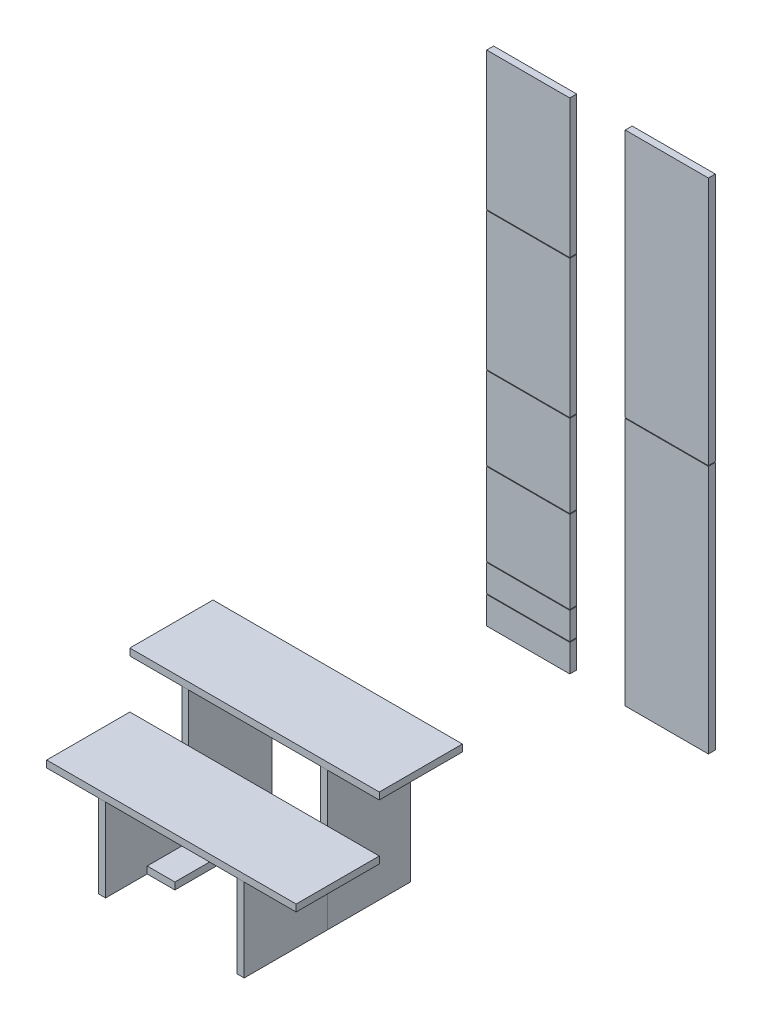
SolidWorks part; units mm, degrees
other "DetailItem1"
ref_plane "Front Plane" through (0, 0, 0) normal (0, 0, 1) x (1, 0, 0)
ref_plane "Top Plane" through (0, 0, 0) normal (0, 1, 0) x (1, 0, 0)
ref_plane "Right Plane" through (0, 0, 0) normal (1, 0, 0) x (0, 0, -1)
sketch "Sketch1" plane through (0, 0, 0) normal (0, 1, 0) x (1, 0, 0)
  line L0 (-254, 0) -> (254, 0) construction
  line L2 (-266.7, 152.4) -> (-241.3, 152.4)
  line L3 (-266.7, 152.4) -> (-266.7, -152.4)
  line L4 (-266.7, -152.4) -> (-241.3, -152.4)
  line L5 (-241.3, 152.4) -> (-241.3, -152.4)
  line L6 (-266.7, 152.4) -> (-241.3, -152.4) construction
  line L7 (-266.7, -152.4) -> (-241.3, 152.4) construction
  line L8 (241.3, 152.4) -> (266.7, 152.4)
  line L9 (241.3, 152.4) -> (241.3, -152.4)
  line L10 (241.3, -152.4) -> (266.7, -152.4)
  line L11 (266.7, 152.4) -> (266.7, -152.4)
  line L12 (241.3, 152.4) -> (266.7, -152.4) construction
  line L13 (241.3, -152.4) -> (266.7, 152.4) construction
  dimension "D1" = 25.4
  dimension "D2" = 304.8
  dimension "D3" = 508
extrude "Boss-Extrude1" add sketch "Sketch1" along normal blind 508
sketch "Sketch2" plane through (0, 508, 0) normal (0, 1, 0) x (1, 0, 0)
  line L0 (-241.3, 152.4) -> (-266.7, 152.4) construction
  line L1 (-457.2, -152.4) -> (457.2, -152.4)
  line L2 (-457.2, -152.4) -> (-457.2, 152.4)
  line L3 (-457.2, 152.4) -> (457.2, 152.4)
  line L4 (457.2, -152.4) -> (457.2, 152.4)
  line L5 (-457.2, -152.4) -> (457.2, 152.4) construction
  line L6 (-457.2, 152.4) -> (457.2, -152.4) construction
  point P0 (0, 0)
  dimension "D1" = 914.4
extrude "Boss-Extrude2" add sketch "Sketch2" along normal blind 25.4 separate body
sketch "Sketch3" plane through (0, 0, 0) normal (0, 1, 0) x (1, 0, 0)
  line L0 (-254, -304.8) -> (254, -304.8) construction
  line L1 (-457.2, -152.4) -> (457.2, -152.4) construction
  line L2 (-266.7, -152.4) -> (-241.3, -152.4)
  line L3 (-266.7, -152.4) -> (-266.7, -457.2)
  line L4 (-266.7, -457.2) -> (-241.3, -457.2)
  line L5 (-241.3, -152.4) -> (-241.3, -457.2)
  line L6 (-266.7, -152.4) -> (-241.3, -457.2) construction
  line L7 (-266.7, -457.2) -> (-241.3, -152.4) construction
  line L8 (241.3, -152.4) -> (266.7, -152.4)
  line L9 (241.3, -152.4) -> (241.3, -457.2)
  line L10 (241.3, -457.2) -> (266.7, -457.2)
  line L11 (266.7, -152.4) -> (266.7, -457.2)
  line L12 (241.3, -152.4) -> (266.7, -457.2) construction
  line L13 (241.3, -457.2) -> (266.7, -152.4) construction
  point P2 (0, -304.8)
  dimension "D1" = 25.4
  dimension "D2" = 304.8
  dimension "D3" = 508
extrude "Boss-Extrude3" add sketch "Sketch3" along normal blind 304.8 separate body
sketch "Sketch4" plane through (0, 304.8, 0) normal (0, 1, 0) x (1, 0, 0)
  line L0 (-457.2, -152.4) -> (457.2, -152.4) construction
  line L1 (-457.2, -457.2) -> (457.2, -457.2)
  line L2 (-457.2, -457.2) -> (-457.2, -152.4)
  line L3 (-457.2, -152.4) -> (457.2, -152.4)
  line L4 (457.2, -457.2) -> (457.2, -152.4)
  line L5 (-457.2, -457.2) -> (457.2, -152.4) construction
  line L6 (-457.2, -152.4) -> (457.2, -457.2) construction
  line L7 (-266.7, -457.2) -> (-241.3, -457.2) construction
  point P0 (0, -304.8)
  dimension "D1" = 914.4
extrude "Boss-Extrude4" add sketch "Sketch4" along normal blind 25.4 separate body
sketch "Sketch5" plane through (0, 0, 0) normal (0, 1, 0) x (1, 0, 0)
  line L0 (0, 0) -> (0, 1117.6) construction
  line L1 (-254, 1117.6) -> (254, 1117.6) construction
  line L3 (-406.4, 1130.3) -> (-101.6, 1130.3)
  line L4 (-406.4, 1130.3) -> (-406.4, 1104.9)
  line L5 (-406.4, 1104.9) -> (-101.6, 1104.9)
  line L6 (-101.6, 1130.3) -> (-101.6, 1104.9)
  line L7 (-406.4, 1130.3) -> (-101.6, 1104.9) construction
  line L8 (-406.4, 1104.9) -> (-101.6, 1130.3) construction
  line L9 (101.6, 1130.3) -> (406.4, 1130.3)
  line L10 (101.6, 1130.3) -> (101.6, 1104.9)
  line L11 (101.6, 1104.9) -> (406.4, 1104.9)
  line L12 (406.4, 1130.3) -> (406.4, 1104.9)
  line L13 (101.6, 1130.3) -> (406.4, 1104.9) construction
  line L14 (101.6, 1104.9) -> (406.4, 1130.3) construction
  point P5 (0, 1117.6)
  dimension "D1" = 25.4
  dimension "D2" = 304.8
  dimension "D3" = 25.4
  dimension "D4" = 304.8
  dimension "D5" = 1117.6
  dimension "D6" = 508
extrude "Boss-Extrude5" add sketch "Sketch5" along normal blind 1828.8 separate body
sketch "Sketch6" plane through (0, 0, -1130.3) normal (0, 0, -1) x (-1, 0, 0)
  line L0 (-406.4, 914.4) -> (-101.6, 914.4)
  line L1 (-406.4, 1828.8) -> (-406.4, 0) construction
  line L2 (-101.6, 1828.8) -> (-101.6, 0) construction
  line L3 (101.6, 1320.8) -> (406.4, 1320.8)
  line L4 (101.6, 1828.8) -> (101.6, 0) construction
  line L5 (406.4, 1828.8) -> (406.4, 0) construction
  line L6 (101.6, 812.8) -> (406.4, 812.8)
  line L7 (101.6, 508) -> (406.4, 508)
  line L8 (101.6, 203.2) -> (406.4, 203.2)
  line L9 (101.6, 101.6) -> (406.4, 101.6)
  line L10 (101.6, 1828.8) -> (406.4, 1828.8) construction
  line L11 (101.6, 0) -> (406.4, 0) construction
  dimension "D1" = 508
  dimension "D2" = 508
  dimension "D3" = 304.8
  dimension "D4" = 304.8
  dimension "D5" = 101.6
sketch "Sketch7" plane through (0, 0, 0) normal (0, -1, 0) x (1, 0, 0)
  line L0 (-241.3, 152.4) -> (241.3, 152.4) construction
  line L1 (241.3, -152.4) -> (241.3, 152.4) construction
  line L2 (-241.3, 304.8) -> (241.3, 304.8)
  line L3 (-241.3, 304.8) -> (-241.3, 0)
  line L4 (-241.3, 0) -> (241.3, 0)
  line L5 (241.3, 304.8) -> (241.3, 0)
  line L6 (-241.3, 304.8) -> (241.3, 0) construction
  line L7 (-241.3, 0) -> (241.3, 304.8) construction
  line L8 (-139.7, 304.8) -> (-139.7, 0)
  line L9 (139.7, 304.8) -> (139.7, 0)
  point P4 (0, 152.4)
  line M7 (-241.3, 152.4) -> (-241.3, 457.2)
  dimension "D1" = 304.8
  dimension "D2" = 101.6
  dimension "D3" = 101.6
extrude "Boss-Extrude6" add sketch "Sketch7" against normal blind 25.4 separate body contours L8 L2 L3 L4 M7 | L2 L9 L4 L5 region at (-190.5, 0, 152.4) region at (190.5, 0, 152.4)
extrude "Cut-Extrude-Thin1" cut sketch "Sketch6" against normal blind 25.4 thin thin type mid plane wall 2.54
equation "\"D3@Sketch1\"=36-16"
equation "\"D3@Sketch3\"=36-16"
